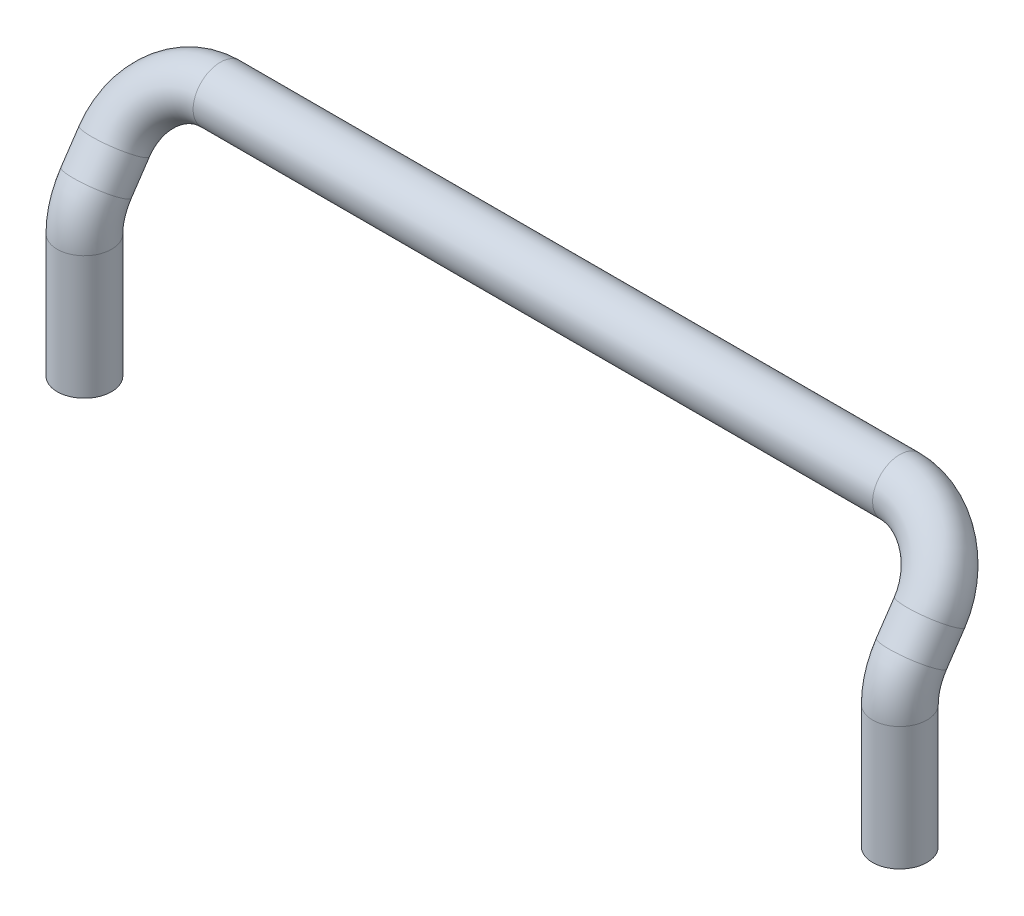
SolidWorks part; units mm, degrees
ref_plane "Front Plane" through (0, 0, 0) normal (0, 0, 1) x (1, 0, 0)
ref_plane "Top Plane" through (0, 0, 0) normal (0, 1, 0) x (1, 0, 0)
ref_plane "Right Plane" through (0, 0, 0) normal (1, 0, 0) x (0, 0, -1)
ref_axis "Axis_X" through (-10.4, 0, 0) along (1, 0, 0)
ref_axis "Axis_Y" through (0, 42, 0) along (0, -1, 0)
ref_axis "Axis_Z" through (0, 0, 0) along (0, 0, 1)
ref_plane "Plane1" through (120, 0, 0) normal (1, 0, 0) x (0, 0, -1)
sketch3d "3DSketch1"
  line L0 (0, 0, 0) -> (0, 18.16, 0)
  line L1 (0, 23.7654, -1.7187) -> (0, 27.7187, -4.3946)
  line L2 (10, 36, -10) -> (110, 36, -10)
  line L3 (120, 27.7187, -4.3946) -> (120, 23.7654, -1.7187)
  line L4 (120, 18.16, 0) -> (120, 0, 0)
  arc A0 (120, 18.16, 0) -> (120, 23.7654, -1.7187) centre (120, 18.16, -10) ccw
  arc A1 (120, 27.7187, -4.3946) -> (110, 36, -10) centre (110, 27.7187, -4.3946) ccw
  arc A2 (0, 27.7187, -4.3946) -> (10, 36, -10) centre (10, 27.7187, -4.3946) ccw
  arc A3 (0, 18.16, 0) -> (0, 23.7654, -1.7187) centre (0, 18.16, -10) ccw
  point P10 (110, 18.16, -10)
  point P13 (120, 36, -10)
  point P15 (110, 33.3241, 3.8867)
  point P18 (0, 36, -10)
  point P19 (10, 22.1133, -12.6759)
  point P23 (-10, 18.16, -10)
  dimension "KSS_3" = 10
  dimension "FIX_2" = 10
  dimension "L" = 120
  dimension "KSS_4" = 36
  dimension "MSM_1" = 18.16
sketch "Sketch2" plane through (0, 0, 0) normal (0, 1, 0) x (1, 0, 0)
  circle A0 centre (0, 0) radius 4
  dimension "D" = 8
sweep "Sweep1" add profiles "Sketch2" path "3DSketch1"
hole_wizard "Tap1" positions "Sketch4" profile "Sketch3" hole size "M4x0.7" standard "JIS"
sketch "Sketch4" plane through (0, 0, 0) normal (0, -1, 0) x (-1, 0, 0)
  point P0 (0, 0)
  point P3 (-120, 0)
sketch "Sketch3" plane through (0, 0, 0) normal (1, 0, 0) x (0, 0, -1)
  line L0 (0, 0) -> (0, 13.242)
  line L1 (0, 13.242) -> (2.067, 12)
  line L2 (2.067, 12) -> (2.067, 0)
  line L5 (2.067, 0) -> (0, 0)
  line L10 (0, 13.242) -> (-2.067, 12) construction
  line L11 (0, -6.35) -> (0, 107.95) construction
  dimension "HSD_1" = 4.134
  dimension "KSS_1" = 12
  dimension "Drill Angle" = 118
cosmetic thread "Thread1" parameters "D_s"=10, "M"=5
cosmetic thread "Thread2" parameters "D_s"=10, "M"=5
equation "\"KSS_1@Sketch3\"= \"D_s@Thread1\" + 2"
equation "\"A\"=18"
equation "\"H\"=40"
equation "\"KSS_3@3DSketch1\"= \"A\" - \"D@Sketch2\""
equation "\"KSS_4@3DSketch1\"= \"H\" - \"D@Sketch2\" / 2"
equation "\"L\"=120.000000"
equation "\"KSS_2@Plane1\" = \"L\""
